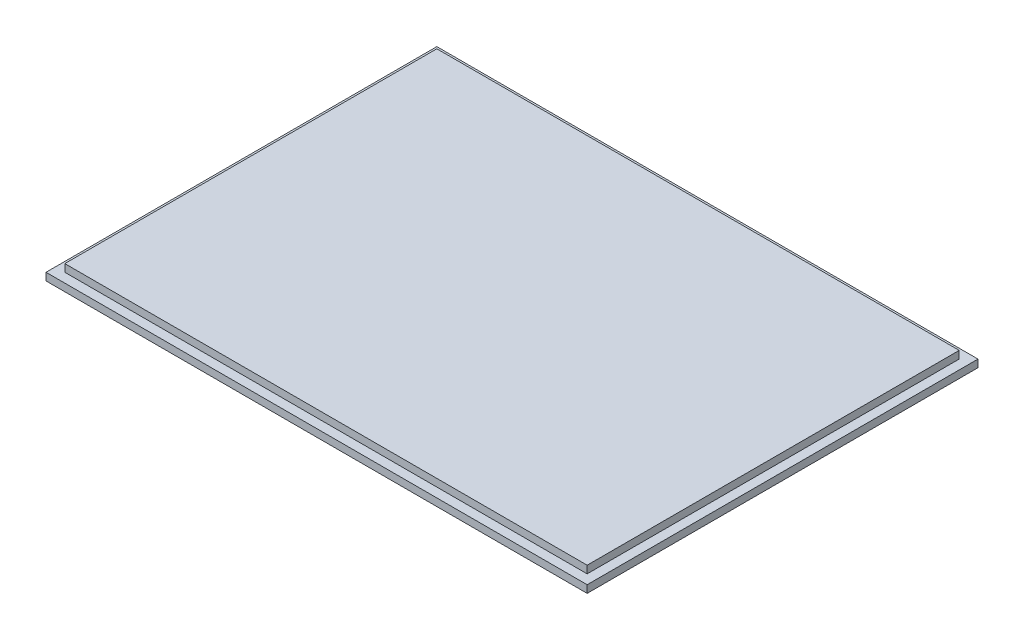
SolidWorks part; units mm, degrees
ref_plane "Alzado" through (0, 0, 0) normal (0, 0, 1) x (1, 0, 0)
ref_plane "Planta" through (0, 0, 0) normal (0, 1, 0) x (1, 0, 0)
ref_plane "Vista lateral" through (0, 0, 0) normal (1, 0, 0) x (0, 0, -1)
sketch "Croquis1" plane through (0, 0, 0) normal (0, 1, 0) x (1, 0, 0)
  line L0 (-1.25, -1.25) -> (-1.25, 50.75)
  line L1 (0, 0) -> (69.5, 0)
  line L2 (0, 0) -> (0, 49.5)
  line L3 (0, 49.5) -> (69.5, 49.5)
  line L4 (69.5, 0) -> (69.5, 49.5)
  line L5 (-1.25, 50.75) -> (70.75, 50.75)
  line L6 (70.75, -1.25) -> (70.75, 50.75)
  line L7 (-1.25, -1.25) -> (70.75, -1.25)
  dimension "D1" = 49.5
  dimension "D2" = 69.5
  dimension "D3" = 1.25
extrude "Saliente-Extruir1" add sketch "Croquis1" along normal blind 1 contours L2 L1 L4 L3 | L0 L5 L6 L7
extrude "Saliente-Extruir3" add sketch "Croquis1<5>" along normal blind 2 contours L1 L4 L3 L2 region at (34.75, 0, -24.75)
sketch "Croquis1<5>" plane through (0, 0, 0) normal (0, 1, 0) x (1, 0, 0) same geometry as "Croquis1"
